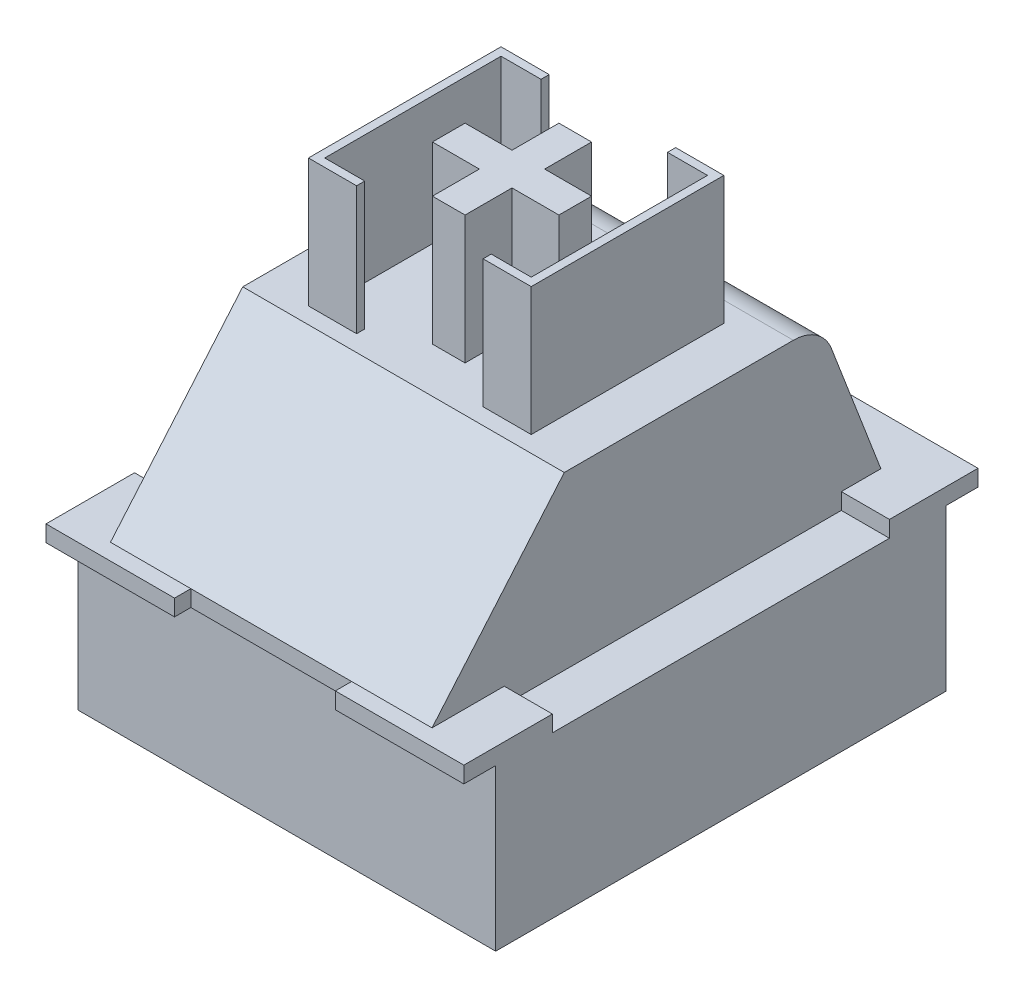
SolidWorks part; units mm, degrees
ref_plane "Alzado" through (0, 0, 0) normal (0, 0, 1) x (1, 0, 0)
ref_plane "Planta" through (0, 0, 0) normal (0, 1, 0) x (1, 0, 0)
ref_plane "Vista lateral" through (0, 0, 0) normal (1, 0, 0) x (0, 0, -1)
sketch "Croquis1" plane through (0, 0, 0) normal (1, 0, 0) x (0, 0, -1)
  line L0 (-3.3765, 7.8359) -> (-7.493, 3.0099)
  line L1 (-7.0104, -2.5019) -> (7.0104, -2.5019)
  line L2 (-7.0104, -2.5019) -> (-7.0104, 2.5019)
  line L4 (7.0104, -2.5019) -> (7.0104, 2.5019)
  line L5 (-7.493, 3.0099) -> (6.477, 3.0099)
  line L7 (-8.001, 2.5019) -> (-7.0104, 2.5019)
  line L8 (-8.001, 2.5019) -> (-8.001, 3.0099)
  line L9 (-8.001, 3.0099) -> (8.001, 3.0099)
  line L10 (8.001, 2.5019) -> (8.001, 3.0099)
  line L11 (6.477, 3.0099) -> (-3.5052, 3.0099)
  line L13 (3.7516, 7.8359) -> (-3.3765, 7.8359)
  line L15 (4.9373, 7.021) -> (6.477, 3.0099)
  line L16 (7.0104, 2.5019) -> (8.001, 2.5019)
  line L17 (-2.8685, 7.8359) -> (3.1259, 7.8359)
  line L18 (-2.8685, 7.8359) -> (-2.8685, 11.8237)
  line L19 (-2.8685, 11.8237) -> (3.1259, 11.8237)
  line L20 (3.1259, 7.8359) -> (3.1259, 11.8237)
  arc A0 (4.9373, 7.021) -> (3.7516, 7.8359) centre (3.7516, 6.5659) ccw
  point P0 (0, 0)
  point P14 (8.001, 2.7559)
  point P19 (4.6245, 7.8359)
  point P20 (-7.0104, 0)
  point P21 (0, -2.5019)
  dimension "D7" = 1.27
  dimension "D1" = 16.002
  dimension "D2" = 0.508
  dimension "D3" = 4.826
  dimension "D4" = 13.97
  dimension "D5" = 8.001
  dimension "D6" = 3.9878
  dimension "D8" = 0.9906
  dimension "D9" = 0.9906
  dimension "D10" = 5.0038
  dimension "D11" = 0.508
  dimension "D12" = 69
  dimension "D13" = 5.9944
  dimension "D14" = 3.9878
  dimension "D15" = 0.508
  dimension "D16" = 14.0208
extrude "Saliente-Extruir1" add sketch "Croquis1" along normal blind 6.5024 and the other way blind 6.5024 contours L4 L16 L10 L9 L5 L8 L7 L2 L1 region at (0, 0.2862, 0)
extrude "Saliente-Extruir2" add sketch "Croquis1<3>" along normal blind 5.0038 and the other way blind 5.0038 contours L15 A0 L13 L0 L5 L9 region at (0, 5.198, 0.005)
sketch "Croquis1<3>" plane through (0, 0, 0) normal (1, 0, 0) x (0, 0, -1) same geometry as "Croquis1"
extrude "Saliente-Extruir3" add sketch "Croquis1<4>" along normal blind 3.4671 and the other way blind 3.4671 contours L13 L20 L19 L18 region at (0, 9.8298, -0.1287)
sketch "Croquis1<4>" plane through (0, 0, 0) normal (1, 0, 0) x (0, 0, -1) same geometry as "Croquis1"
sketch "Croquis2" plane through (0, 3.0099, 0) normal (0, 1, 0) x (1, 0, 0)
  line L0 (0, -8.2448) -> (0, 8.2448) construction
  line L1 (-6.5024, -8.001) -> (6.5024, -8.001) construction
  line L2 (-2.5019, -8.001) -> (2.5019, -8.001)
  line L3 (-2.5019, -8.001) -> (-2.5019, -7.493)
  line L4 (-2.5019, -7.493) -> (2.5019, -7.493)
  line L5 (2.5019, -8.001) -> (2.5019, -7.493)
  line L6 (-5.0038, -7.493) -> (5.0038, -7.493) construction
  line L7 (-6.5024, 8.001) -> (6.5024, 8.001) construction
  line L8 (-2.5019, 8.001) -> (2.5019, 8.001)
  line L9 (-2.5019, 8.001) -> (-2.5019, 6.477)
  line L10 (-2.5019, 6.477) -> (2.5019, 6.477)
  line L11 (2.5019, 8.001) -> (2.5019, 6.477)
  line L12 (-5.0038, 6.477) -> (5.0038, 6.477) construction
  line L13 (-6.5024, -8.001) -> (-6.5024, 8.001) construction
  line L14 (-6.5024, 5.2451) -> (-5.0038, 5.2451)
  line L15 (-6.5024, 5.2451) -> (-6.5024, -5.2451)
  line L16 (-6.5024, -5.2451) -> (-5.0038, -5.2451)
  line L17 (-5.0038, 5.2451) -> (-5.0038, -5.2451)
  line L18 (-5.0038, -7.493) -> (-5.0038, 6.477) construction
  line L19 (5.0038, -7.493) -> (5.0038, 6.477) construction
  line L20 (5.0038, 5.2451) -> (6.5024, 5.2451)
  line L21 (5.0038, 5.2451) -> (5.0038, -5.2451)
  line L22 (5.0038, -5.2451) -> (6.5024, -5.2451)
  line L23 (6.5024, 5.2451) -> (6.5024, -5.2451)
  line L24 (6.5024, -8.001) -> (6.5024, 8.001) construction
  point P4 (0, 0)
  point P21 (0, 8.001)
  point P22 (0, -8.001)
  point P39 (-6.5024, 0)
  point P40 (6.5024, 0)
  dimension "D1" = 5.0038
  dimension "D2" = 5.0038
  dimension "D3" = 10.4902
  dimension "D4" = 10.4902
extrude "Cortar-Extruir1" cut sketch "Croquis2" against normal up to surface (0.508 mm away) up to face at (0, 2.5019, -7.5057)
sketch "Croquis3" plane through (0, 11.8237, 0) normal (0, 1, 0) x (1, 0, 0)
  line L0 (-3.4671, 3.1259) -> (-3.4671, -2.8685)
  line L1 (-3.4671, -2.8685) -> (-1.9685, -2.8685)
  line L2 (-3.4671, -2.8685) -> (3.4671, -2.8685) construction
  line L3 (-3.4671, 3.1259) -> (-1.9685, 3.1259)
  line L4 (-3.4671, 3.1259) -> (3.4671, 3.1259) construction
  line L5 (-3.2131, -2.6145) -> (-1.9685, -2.6145)
  line L6 (-3.2131, 2.8719) -> (-3.2131, -2.6145)
  line L7 (-3.2131, 2.8719) -> (-1.9685, 2.8719)
  line L8 (-1.9685, -2.8685) -> (-1.9685, -2.6145)
  line L9 (-1.9685, 3.1259) -> (-1.9685, 2.8719)
  line L10 (0, 0) -> (0, 5.5715) construction
  line L11 (0.508, 1.9685) -> (-0.508, 1.9685)
  line L12 (-0.508, 1.9685) -> (-0.508, 0.508)
  line L13 (-0.508, 0.508) -> (-1.9685, 0.508)
  line L14 (-1.9685, 0.508) -> (-1.9685, -0.508)
  line L15 (-1.9685, -0.508) -> (-0.508, -0.508)
  line L16 (-0.508, -0.508) -> (-0.508, -1.9685)
  line L17 (-0.508, -1.9685) -> (0.508, -1.9685)
  line L18 (3.2131, 2.8719) -> (3.2131, -2.6145)
  line L19 (3.2131, 2.8719) -> (1.9685, 2.8719)
  line L20 (1.9685, 3.1259) -> (1.9685, 2.8719)
  line L21 (3.4671, 3.1259) -> (1.9685, 3.1259)
  line L22 (3.4671, 3.1259) -> (3.4671, -2.8685)
  line L23 (3.4671, -2.8685) -> (1.9685, -2.8685)
  line L24 (1.9685, -2.8685) -> (1.9685, -2.6145)
  line L25 (3.2131, -2.6145) -> (1.9685, -2.6145)
  line L26 (0.508, -0.508) -> (0.508, -1.9685)
  line L27 (1.9685, -0.508) -> (0.508, -0.508)
  line L28 (1.9685, 0.508) -> (1.9685, -0.508)
  line L29 (0.508, 0.508) -> (1.9685, 0.508)
  line L30 (0.508, 1.9685) -> (0.508, 0.508)
  point P28 (-1.9685, 0)
  point P35 (0, -1.9685)
  point P43 (0, 1.9685)
  dimension "D2" = 0.508
  dimension "D3" = 1.016
  dimension "D4" = 0.254
  dimension "D5" = 1.4986
  dimension "D1" = 0.254
  dimension "D6" = 0.254
extrude "Cortar-Extruir2" cut sketch "Croquis3" against normal up to surface (3.9878 mm away) flip side to cut up to face at (0, 7.8359, -0.1875)
